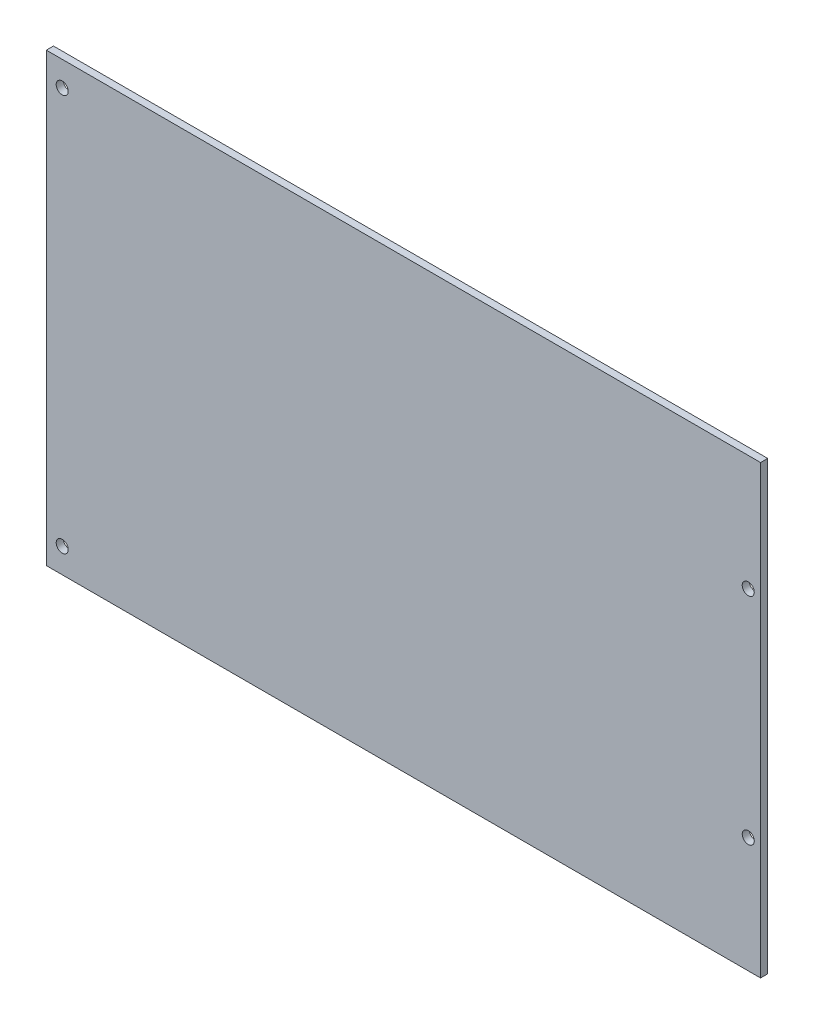
SolidWorks part; units mm, degrees
material "Fibre de verre A"
ref_plane "Plan de face" through (0, 0, 0) normal (0, 0, 1) x (1, 0, 0)
ref_plane "Plan de dessus" through (0, 0, 0) normal (0, 1, 0) x (1, 0, 0)
ref_plane "Plan de droite" through (0, 0, 0) normal (1, 0, 0) x (0, 0, -1)
sketch "Esquisse1" plane through (0, 0, 0) normal (0, 0, 1) x (1, 0, 0)
  line L1 (-80, 50) -> (80, 50)
  line L2 (-80, 50) -> (-80, -50)
  line L3 (-80, -50) -> (80, -50)
  line L4 (80, 50) -> (80, -50)
  line L5 (-80, 50) -> (80, -50) construction
  line L6 (-80, -50) -> (80, 50) construction
  point P0 (0, 0)
  dimension "D1" = 160
  dimension "D2" = 100
extrude "Boss.-Extru.1" add sketch "Esquisse1" along normal blind 1.6
hole_wizard "Diamètre du perçage Ø2.7 (2.7)1" positions "Esquisse3" profile "Esquisse2" hole size "Ø2.7" standard "Iso" end condition through all
sketch "Esquisse3" plane through (0, 0, 1.6) normal (0, 0, 1) x (1, 0, 0)
  line L0 (-80, 50) -> (-80, -50) construction
  line L1 (-76.43, 44.45) -> (-76.43, -44.45) construction
  line L3 (0, 0) -> (-76.43, 0) construction
  point P0 (-76.43, 44.45)
  point P2 (-76.43, -44.45)
  dimension "D1" = 3.57
  dimension "D2" = 88.9
sketch "Esquisse2" plane through (-76.43, 44.45, 1.6) normal (1, 0, 0) x (0, -1, 0)
  line L0 (0, 0) -> (0, 1.6)
  line L1 (0, 1.6) -> (1.35, 1.6)
  line L2 (1.35, 1.6) -> (1.35, 0)
  line L5 (1.35, 0) -> (0, 0)
  line L11 (0, -6.35) -> (0, 107.95) construction
  dimension "Diamètre du perçage jusqu'au prochain" = 2.7
  dimension "Profondeur du perçage jusqu'au prochain" = 1.6
hole_wizard "Diamètre du perçage Ø2.7 (2.7)2" positions "Esquisse5" profile "Esquisse4" hole size "Ø2.7" standard "Iso" end condition through all
sketch "Esquisse5" plane through (0, 0, 1.6) normal (0, 0, 1) x (1, 0, 0)
  line L0 (77.24, 24.13) -> (77.24, -24.13) construction
  line L2 (80, 0) -> (77.24, 0) construction
  line L3 (80, -50) -> (80, 50) construction
  point P0 (77.24, 24.13)
  point P2 (77.24, -24.13)
  dimension "D1" = 48.26
  dimension "D2" = 2.76
sketch "Esquisse4" plane through (77.24, 24.13, 1.6) normal (1, 0, 0) x (0, -1, 0)
  line L0 (0, 0) -> (0, 1.6)
  line L1 (0, 1.6) -> (1.35, 1.6)
  line L2 (1.35, 1.6) -> (1.35, 0)
  line L5 (1.35, 0) -> (0, 0)
  line L11 (0, -6.35) -> (0, 107.95) construction
  dimension "Diamètre du perçage jusqu'au prochain" = 2.7
  dimension "Profondeur du perçage jusqu'au prochain" = 1.6
